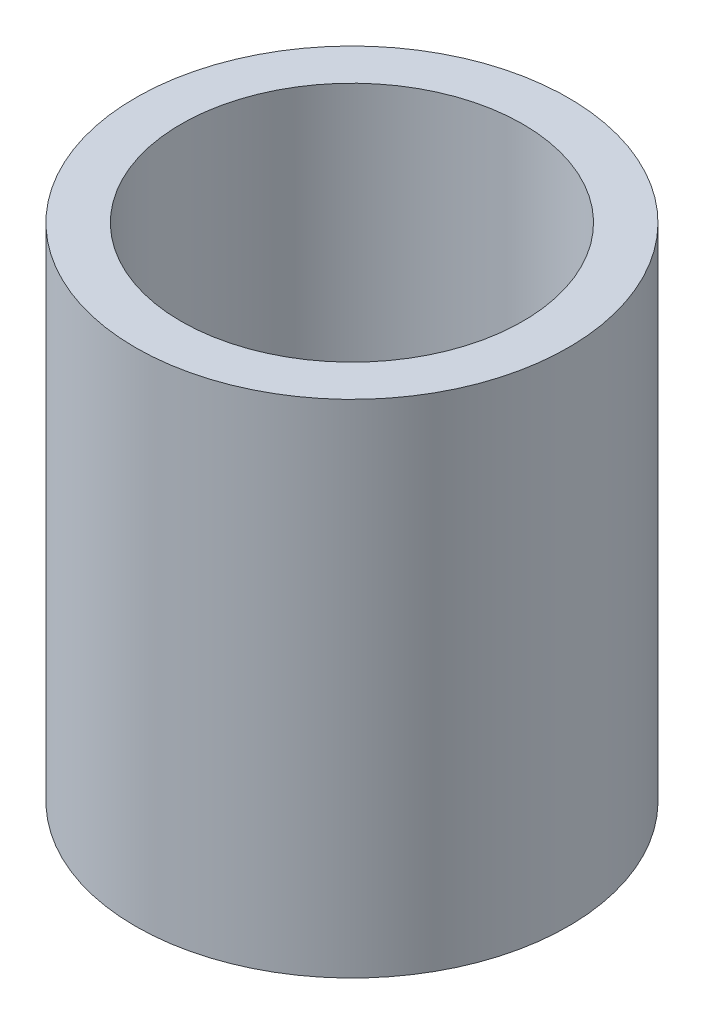
SolidWorks part; units mm, degrees
ref_plane "Front Plane" through (0, 0, 0) normal (0, 0, 1) x (1, 0, 0)
ref_plane "Top Plane" through (0, 0, 0) normal (0, 1, 0) x (1, 0, 0)
ref_plane "Right Plane" through (0, 0, 0) normal (1, 0, 0) x (0, 0, -1)
sketch "Sketch1" plane through (0, 0, 0) normal (0, 1, 0) x (1, 0, 0)
  line L0 (-37.5, 0) -> (37.5, 0)
  line L1 (0, -17.167) -> (0, 17.167)
  circle A0 centre (0, 0) radius 37.5
  circle A1 centre (0, 0) radius 47.5
  point P5 (0, 0)
  point P7 (0, 0)
  point P10 (47.5, 0)
  dimension "D1" = 10
  dimension "D2" = 75
extrude "Boss-Extrude1" add sketch "Sketch1" along normal blind 110 contours A1 A0 region at (-46.1565, 0, 0)
sketch "Sketch2" plane through (0, 0, 0) normal (0, -1, 0) x (1, 0, 0)
  circle A0 centre (0, 0) radius 5.25
  circle A1 centre (0, 0) radius 37.5 construction
  circle A2 centre (0, 0) radius 37.5
  point P4 (37.5, 0)
  dimension "D1" = 10.5
extrude "Boss-Extrude2" add sketch "Sketch2" against normal blind 5
